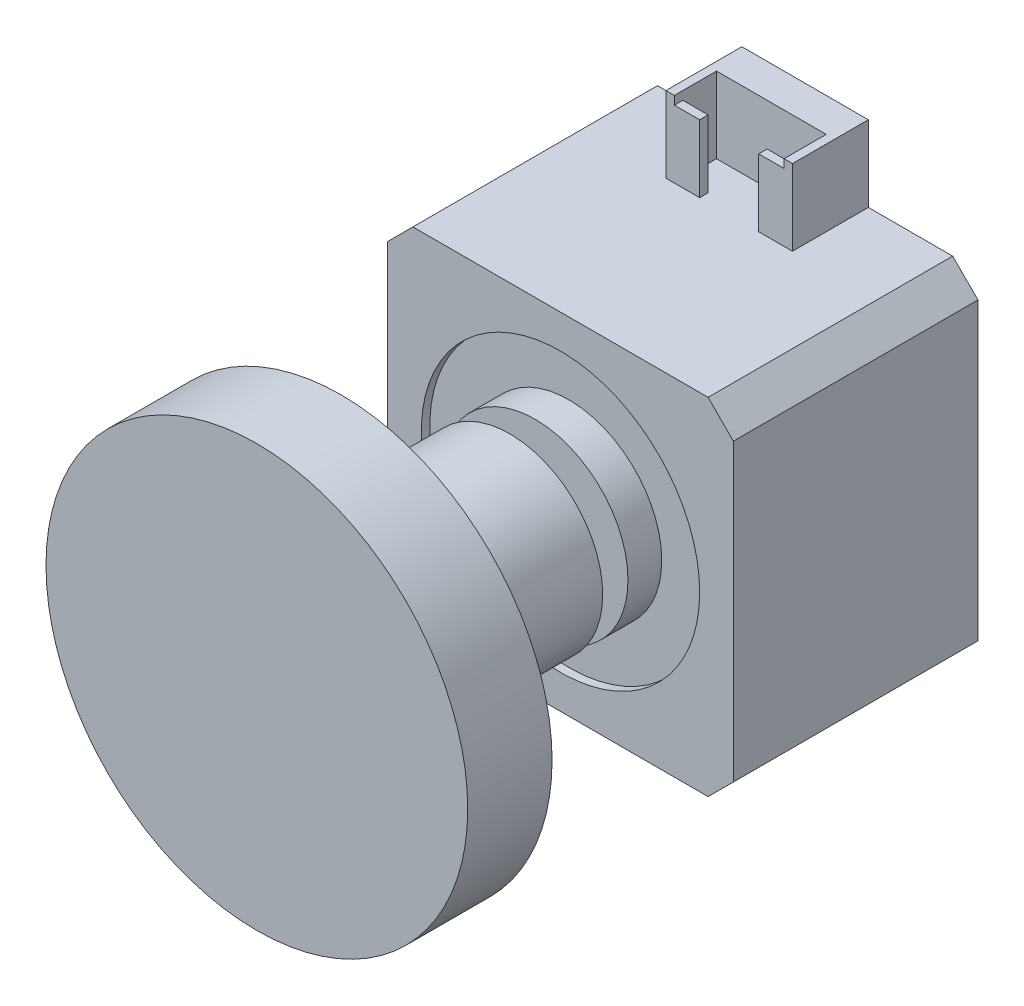
SolidWorks part; units mm, degrees
ref_plane "Plan de face" through (0, 0, 0) normal (0, 0, 1) x (1, 0, 0)
ref_plane "Plan de dessus" through (0, 0, 0) normal (0, 1, 0) x (1, 0, 0)
ref_plane "Plan de droite" through (0, 0, 0) normal (1, 0, 0) x (0, 0, -1)
sketch "Esquisse1" plane through (0, 0, 0) normal (0, 0, 1) x (1, 0, 0)
  line L1 (0, 0) -> (41, 0)
  line L2 (0, 0) -> (0, 41)
  line L3 (0, 41) -> (41, 41)
  line L4 (41, 0) -> (41, 41)
  dimension "D1" = 41
  dimension "D2" = 41
extrude "Boss.-Extru.1" add sketch "Esquisse1" along normal blind 29
sketch "Esquisse2" plane through (0, 0, 29) normal (0, 0, 1) x (1, 0, 0)
  line L0 (0, 41) -> (0, 0) construction
  line L2 (41, 41) -> (0, 41) construction
  circle A0 centre (20.5, 20.5) radius 16.5
  circle A1 centre (20.5, 20.5) radius 11
  circle A2 centre (20.5, 20.5) radius 2.5
  dimension "D1" = 33
  dimension "D2" = 22
  dimension "D3" = 5
  dimension "D4" = 20.5
  dimension "D5" = 20.5
extrude "Enlèv. mat.-Extru.1" cut sketch "Esquisse2" against normal blind 1 contours A0 A1 region at (4.4667, 20.5, 29)
extrude "Boss.-Extru.2" add sketch "Esquisse2<3>" along normal blind 3 contours A1 A2 region at (9.8111, 20.5, 29)
sketch "Esquisse2<3>" plane through (0, 0, 29) normal (0, 0, 1) x (1, 0, 0) same geometry as "Esquisse2"
extrude "Boss.-Extru.3" add sketch "Esquisse2<4>" along normal blind 6 contours A2 region at (20.5, 20.5, 29)
sketch "Esquisse2<4>" plane through (0, 0, 29) normal (0, 0, 1) x (1, 0, 0) same geometry as "Esquisse2"
sketch "Esquisse7" plane through (0, 0, 35) normal (0, 0, 1) x (1, 0, 0)
  circle A0 centre (20.5, 20.5) radius 11
  point P3 (0, 0)
extrude "Boss.-Extru.4" add sketch "Esquisse7" along normal blind 20
sketch "Esquisse8" plane through (0, 0, 55) normal (0, 0, 1) x (1, 0, 0)
sketch "Esquisse9" plane through (0, 0, 55) normal (0, 0, 1) x (1, 0, 0)
  circle A0 centre (20.5, 20.5) radius 25
  dimension "D1" = 50
extrude "Boss.-Extru.5" add sketch "Esquisse9" along normal blind 10
chamfer "Chanfrein1" distance 3 angle 45 4 edges at (41, 41, 14.5) (41, 0, 14.5) (0, 0, 14.5) (0, 41, 14.5)
sketch "Esquisse10" plane through (0, 41, 0) normal (0, 1, 0) x (1, 0, 0)
  line L0 (38, 0) -> (3, 0) construction
  line L1 (28, 0) -> (13, 0)
  line L2 (28, 0) -> (28, -9)
  line L3 (28, -9) -> (13, -9)
  line L4 (13, 0) -> (13, -9)
  line L5 (0, -29) -> (0, 0) construction
  line L6 (41, 0) -> (41, -29) construction
  line L8 (27, -8) -> (14, -8)
  line L9 (27, -8) -> (27, -4)
  line L10 (27, -4) -> (14, -4)
  line L11 (14, -8) -> (14, -4)
  point P14 (28, -4.5)
  dimension "D1" = 13
  dimension "D2" = 13
  dimension "D3" = 9
  dimension "D4" = 4
  dimension "D5" = 1
  dimension "D6" = 1
  dimension "D7" = 1
extrude "Boss.-Extru.6" add sketch "Esquisse10" along normal blind 9
sketch "Esquisse11" plane through (0, 0, 9) normal (0, 0, 1) x (1, 0, 0)
  line L0 (13, 41) -> (28, 41) construction
  line L1 (24, 41) -> (17, 41)
  line L2 (24, 41) -> (24, 50)
  line L3 (24, 50) -> (17, 50)
  line L4 (17, 41) -> (17, 50)
  line L5 (13, 50) -> (13, 41) construction
  line L6 (28, 50) -> (28, 41) construction
  line L7 (13, 50) -> (28, 50) construction
  line L9 (24, 50) -> (27, 50)
  line L10 (24, 50) -> (24, 49)
  line L11 (24, 49) -> (27, 49)
  line L12 (27, 50) -> (27, 49)
  line L13 (17, 50) -> (14, 50)
  line L14 (17, 50) -> (17, 49)
  line L15 (17, 49) -> (14, 49)
  line L16 (14, 50) -> (14, 49)
  line M13 (13, 41) -> (28, 41)
  line M15 (28, 50) -> (13, 50)
  dimension "D1" = 0
  dimension "D2" = 4
  dimension "D3" = 4
  dimension "D4" = 0
  dimension "D5" = 1
  dimension "D6" = 1
  dimension "D7" = 1
  dimension "D8" = 1
extrude "Enlèv. mat.-Extru.3" cut sketch "Esquisse11" against normal blind 2 contours L12 L2 L11 M15 | L4 L2 M13 M15 | L14 L15 L16 L13 region at (20.5, 45.5, 9) region at (25.5, 49.5, 9)
